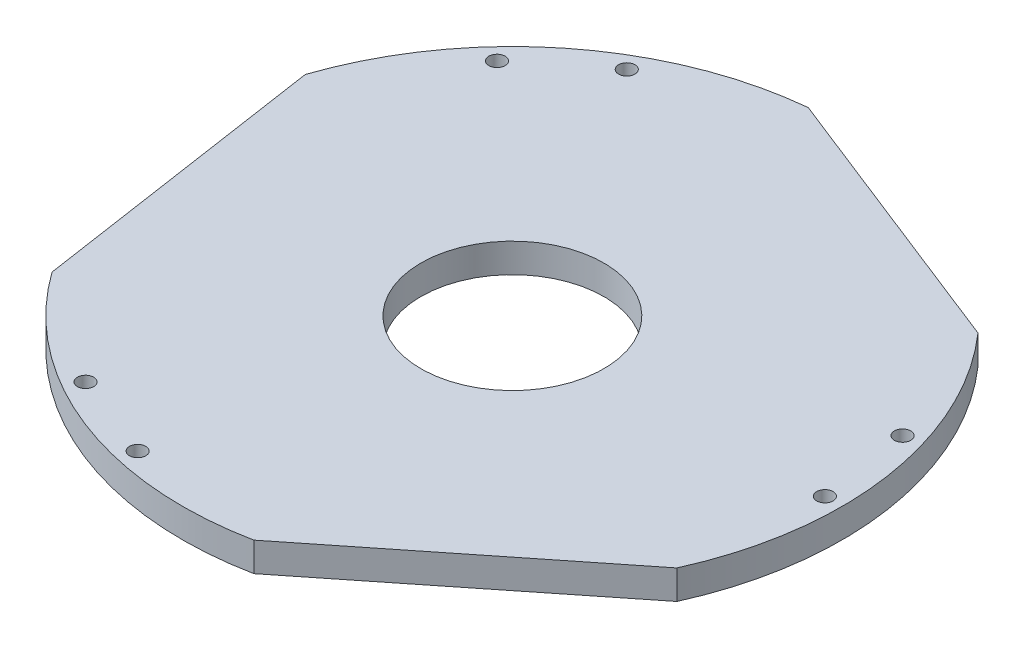
SolidWorks part; units mm, degrees
material "Oak"
ref_plane "Front Plane" through (0, 0, 0) normal (0, 0, 1) x (1, 0, 0)
ref_plane "Top Plane" through (0, 0, 0) normal (0, 1, 0) x (1, 0, 0)
ref_plane "Right Plane" through (0, 0, 0) normal (1, 0, 0) x (0, 0, -1)
sketch "Sketch1" plane through (0, 0, 0) normal (0, 0, 1) x (1, 0, 0)
  line L0 (0, -200000) -> (0, 218797.9879) construction
  line L1 (144.145, -24.4122) -> (144.145, -37.1122) construction
  line L2 (0, -24.4122) -> (144.145, -24.4122) construction
  line L3 (144.145, -37.1122) -> (0, -37.1122) construction
  line L4 (0, -200000) -> (0, 218797.9879) construction
  line L5 (144.145, -24.4122) -> (144.145, -37.1122)
  line L6 (0, -24.4122) -> (144.145, -24.4122)
  line L7 (144.145, -37.1122) -> (0, -37.1122)
  line L8 (0, -24.4122) -> (0, -37.1122)
revolve "Revolve1" add sketch "Sketch1" angle 360 about L4
hole_wizard "9/32 (0.28125) Diameter Hole1" positions "Sketch2" profile "Sketch3" hole size "9/32" standard "ANSI Inch" end condition up to next
sketch "Sketch2" plane through (0, -24.4122, 0) normal (0, 1, 0) x (1, 0, 0)
  line L0 (0, 0) -> (136.525, 0) construction
  line L3 (0, 0) -> (-68.2625, -118.2341) construction
  line L6 (0, 0) -> (-68.2625, 118.2341) construction
  line L7 (-99.8481, 93.1098) -> (0, 0) construction
  line L9 (0, 0) -> (-30.7114, -133.0259) construction
  line L12 (0, 0) -> (130.5595, 39.916) construction
  circle A0 centre (0, 0) radius 136.525
  point P0 (136.525, 0)
  point P2 (-68.2625, -118.2341)
  point P4 (-68.2625, 118.2341)
  point P32 (-99.8481, 93.1098)
  point P57 (130.5595, 39.916)
  point P60 (-30.7114, -133.0259)
  dimension "D3" = 17
  dimension "D1" = 120
  dimension "D2" = 120
  dimension "D4" = 120
  dimension "D5" = 120
sketch "Sketch3" plane through (136.525, -24.4122, 0) normal (1, 0, 0) x (0, 0, 1)
  line L0 (0, 0) -> (0, 12.7)
  line L1 (0, 12.7) -> (3.5719, 12.7)
  line L2 (3.5719, 12.7) -> (3.5719, 0)
  line L5 (3.5719, 0) -> (0, 0)
  line L11 (0, -6.35) -> (0, 107.95) construction
  dimension "Thru Hole Dia." = 7.1437
  dimension "Thru Hole Depth" = 12.7
sketch "Sketch4" plane through (0, -24.4122, 0) normal (0, 1, 0) x (1, 0, 0)
  line L0 (253.7221, 37.919) -> (-94.0222, -238.6893)
  line L1 (-94.0222, -238.6893) -> (-159.6999, 200.7703)
  line L2 (-159.6999, 200.7703) -> (253.7221, 37.919)
  line L3 (253.7221, 37.919) -> (0, 0) construction
  line L4 (130.5595, 39.916) -> (136.525, 0) construction
  circle A0 centre (0, 0) radius 128.27 construction
  point P6 (133.5423, 19.958)
  dimension "D1" = 256.54
extrude "Cut-Extrude1" cut sketch "Sketch4" against normal through all flip side to cut
sketch "Sketch6" plane through (0, -24.4122, 0) normal (0, 1, 0) x (1, 0, 0)
  circle A0 centre (0, 0) radius 40
  dimension "D1" = 80
extrude "Cut-Extrude2" cut sketch "Sketch6" against normal through all
